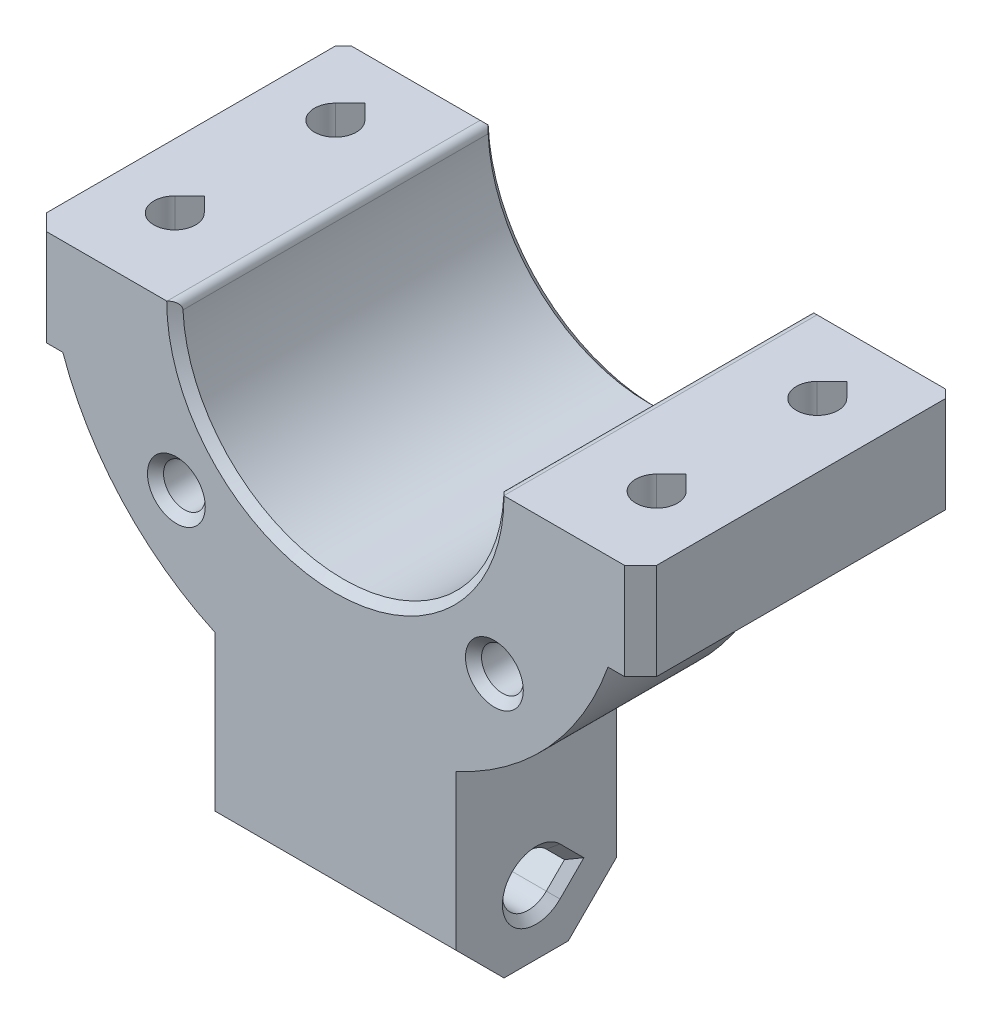
SolidWorks part; units mm, degrees
ref_plane "前视基准面" through (0, 0, 0) normal (0, 0, 1) x (1, 0, 0)
ref_plane "上视基准面" through (0, 0, 0) normal (0, 1, 0) x (1, 0, 0)
ref_plane "右视基准面" through (0, 0, 0) normal (1, 0, 0) x (0, 0, -1)
sketch "草图1" plane through (0, 0, 0) normal (0, 0, 1) x (1, 0, 0)
  line L0 (0, 34.6078) -> (0, -34.6078) construction
  line L1 (-30.8999, 0) -> (31.5242, 0) construction
  line L2 (-10, 0) -> (-19, 0)
  line L3 (-19, 0) -> (-19, -6)
  line L4 (-19, -6) -> (-13.7477, -6)
  line L5 (-16, 0) -> (-16, -3.9162) construction
  line L6 (-14.9, 0) -> (-14.9, -4.2934) construction
  line L7 (-14, 0) -> (-14, 2.8301) construction
  line L8 (-7.5, -12.9904) -> (-7.5, -29)
  line L9 (-7.5, -29) -> (7.5, -29)
  line L10 (-7.5, -25) -> (0, -25) construction
  line L11 (-7.5, -23.4) -> (0, -23.4) construction
  line L12 (-7.5, -22) -> (-10, -22) construction
  line L13 (7.5, -12.9904) -> (7.5, -29)
  line L14 (19, -6) -> (13.7477, -6)
  line L15 (19, 0) -> (19, -6)
  line L16 (10, 0) -> (19, 0)
  arc A0 (-10, 0) -> (10, 0) centre (0, 0) ccw
  arc A2 (-13.7477, -6) -> (-7.5, -12.9904) centre (0, 0) ccw
  arc A3 (13.7477, -6) -> (7.5, -12.9904) centre (0, 0) cw
  point P29 (0, -29)
  dimension "D1" = 10
  dimension "D2" = 38
  dimension "D3" = 9
  dimension "D5" = 1.1
  dimension "D4" = 15
  dimension "D7" = 5
  dimension "D6" = 2
  dimension "D8" = 25
  dimension "D9" = 1.6
  dimension "D10" = 3
  dimension "D11" = 4
  dimension "D12" = 32
  dimension "D13" = 6
extrude "凸台-拉伸1" add sketch "草图1" along normal blind 10
sketch "草图3" plane through (7.5, 0, 0) normal (1, 0, 0) x (0, 0, -1)
  line L0 (0, -25) -> (-5, -25) construction
  line L1 (0, -29) -> (0, -12.9904) construction
  line L2 (-10, -29) -> (0, -29) construction
  line L3 (-3.8686, -23.8686) -> (-2.7373, -25)
  line L4 (-3.8686, -26.1314) -> (-2.7373, -25)
  arc A0 (-3.8686, -23.8686) -> (-3.8686, -26.1314) centre (-5, -25) ccw
  dimension "D3" = 3.2
  dimension "D1" = 4
  dimension "D2" = 5
  dimension "D4" = 45
extrude "切除-拉伸1" cut sketch "草图3" against normal blind 54
sketch "草图4" plane through (0, 0, 0) normal (0, 1, 0) x (1, 0, 0)
  line L0 (10, -5) -> (-19, -5) construction
  line L1 (10, -10) -> (10, 0) construction
  line L3 (0, 0) -> (0, -23.0766) construction
  line L4 (-15, -5) -> (-15, -3.1615) construction
  line L5 (-15, -3.1615) -> (-15.9192, -4.0808)
  line L6 (-15, -3.1615) -> (-14.0808, -4.0808)
  line L7 (15, -5) -> (15, -3.1615) construction
  line L8 (15, -3.1615) -> (14.0808, -4.0808)
  line L9 (15, -3.1615) -> (15.9192, -4.0808)
  line L10 (-19, -10) -> (-19, 0) construction
  arc A0 (-15.9192, -4.0808) -> (-14.0808, -4.0808) centre (-15, -5) ccw
  arc A1 (15.9192, -4.0808) -> (14.0808, -4.0808) centre (15, -5) cw
  dimension "D1" = 30
  dimension "D2" = 2.6
  dimension "D3" = 45
extrude "切除-拉伸2" cut sketch "草图4" against normal blind 54
sketch "草图5" plane through (0, 0, 0) normal (0, 0, -1) x (-1, 0, 0)
  line L0 (0, 500) -> (0, -500) construction
  line L1 (-500, 0) -> (500, 0) construction
  line L2 (-15, 0) -> (-10, 0)
  line L3 (10, 0) -> (15, 0)
  arc A0 (-10, 0) -> (10, 0) centre (0, 0) ccw construction
  arc A1 (-10, 0) -> (10, 0) centre (0, 0) ccw
  arc A2 (-15, 0) -> (15, 0) centre (0, 0) ccw
  arc A3 (-13.7477, -6) -> (-7.5, -12.9904) centre (0, 0) ccw construction
extrude "凸台-拉伸2" add sketch "草图5" along normal blind 10
sketch "草图6" plane through (0, 0, 10) normal (0, 0, 1) x (1, 0, 0)
  line L0 (0, 500) -> (0, -500) construction
  line L1 (0, 0) -> (15, 0) construction
  line L4 (-13.7477, -6) -> (-16.9706, -6)
  line L5 (0, 0) -> (-53.17, 0) construction
  line L6 (13.7477, -6) -> (16.9706, -6)
  arc A0 (-16.9706, -6) -> (16.9706, -6) centre (0, 0) ccw
  arc A1 (-13.7477, -6) -> (13.7477, -6) centre (0, 0) ccw
  dimension "D2" = 3
extrude "凸台-拉伸3" add sketch "草图6" against normal blind 10
sketch "草图7" plane through (0, 0, 0) normal (0, 0, -1) x (-1, 0, 0)
  line L0 (-19, 0) -> (-19, -6)
  line L1 (-19, -6) -> (-13.7477, -6)
  line L2 (-19, 0) -> (-15, 0)
  line L3 (0, 500) -> (0, -500) construction
  line L4 (-500, 0) -> (500, 0) construction
  line L5 (19, 0) -> (15, 0)
  line L6 (19, -6) -> (13.7477, -6)
  line L7 (19, 0) -> (19, -6)
  arc A0 (-15, 0) -> (15, 0) centre (0, 0) ccw construction
  arc A1 (-15, 0) -> (-13.7477, -6) centre (0, 0) ccw
  arc A2 (15, 0) -> (13.7477, -6) centre (0, 0) cw
  line M2 (19, -6) -> (19, 0)
  line M3 (19, 0) -> (15, 0)
  arc M4 (15, 0) -> (-15, 0) centre (0, 0) cw
  line M5 (-15, 0) -> (-19, 0)
  line M6 (-19, 0) -> (-19, -6)
  line M7 (-19, -6) -> (-16.9706, -6)
  line M13 (16.9706, -6) -> (19, -6)
extrude "凸台-拉伸4" add sketch "草图7" along normal blind 10 contours L1 M7 M4 M5 M6 | L6 M13 M2 M3 M4 region at (16.7793, -3.1407, 0) region at (-16.7793, -3.1407, 0)
sketch "草图8" plane through (0, 0, 0) normal (0, 1, 0) x (1, 0, 0)
  line L0 (0, 500) -> (0, -500) construction
  line L1 (-500, 0) -> (500, 0) construction
  line L2 (-15, -5) -> (-15, 5) construction
  line L3 (-15, 5) -> (-15, 6.8385) construction
  line L4 (-15, 6.8385) -> (-15.9192, 5.9192)
  line L5 (-15, 6.8385) -> (-14.0808, 5.9192)
  line L6 (15, 5) -> (15, 6.8385) construction
  line L7 (15, 6.8385) -> (14.0808, 5.9192)
  line L8 (15, 6.8385) -> (15.9192, 5.9192)
  arc A0 (-15.9192, 5.9192) -> (-14.0808, 5.9192) centre (-15, 5) ccw
  arc A1 (15.9192, 5.9192) -> (14.0808, 5.9192) centre (15, 5) cw
  dimension "D1" = 10
  dimension "D2" = 2.6
  dimension "D3" = 45
extrude "切除-拉伸3" cut sketch "草图8" against normal blind 10
sketch "草图9" plane through (0, 0, 10) normal (0, 0, 1) x (1, 0, 0)
  line L0 (0, 500) -> (0, -500) construction
  line L1 (-500, 0) -> (500, 0) construction
  line L2 (0, 0) -> (-9.8995, -9.8995) construction
  circle A0 centre (0, 0) radius 14 construction
  circle A1 centre (-9.8995, -9.8995) radius 1.3
  circle A2 centre (9.8995, -9.8995) radius 1.3
  dimension "D1" = 28
  dimension "D3" = 2.6
  dimension "D2" = 45
extrude "切除-拉伸4" cut sketch "草图9" against normal blind 8
chamfer "倒角1" distance 3 angle 45 1 edges at (0, -15, 0)
chamfer "倒角2" distance 3 angle 45 2 edges at (0, -29, 0) (0, -29, 10)
chamfer "倒角3" distance 1 angle 45 4 edges at (-19, -3, -10) (-19, -3, 10) (19, -3, -10) (19, -3, 10)
chamfer "倒角4" distance 0.5 angle 45 17 edges at (-7.5, -24.4343, 3.3029) (-7.5, -25.5657, 3.3029) (-7.5, -25, 6.6) (7.5, -24.4343, 3.3029) (7.5, -25.5657, 3.3029) (7.5, -25, 6.6) (-15.8739, -6, -10) (0, -15, -10) (15.8739, -6, -10) (14, 0, -10) (-14, 0, -10) (0, -10, -10) (0, -10, 10) (8.5995, -9.8995, 10) (8.5995, -9.8995, 2) (-8.5995, -9.8995, 10) (-8.5995, -9.8995, 2)
fillet "圆角1" radius 0.5 2 edges at (10, 0, 0) (-10, 0, 0)
